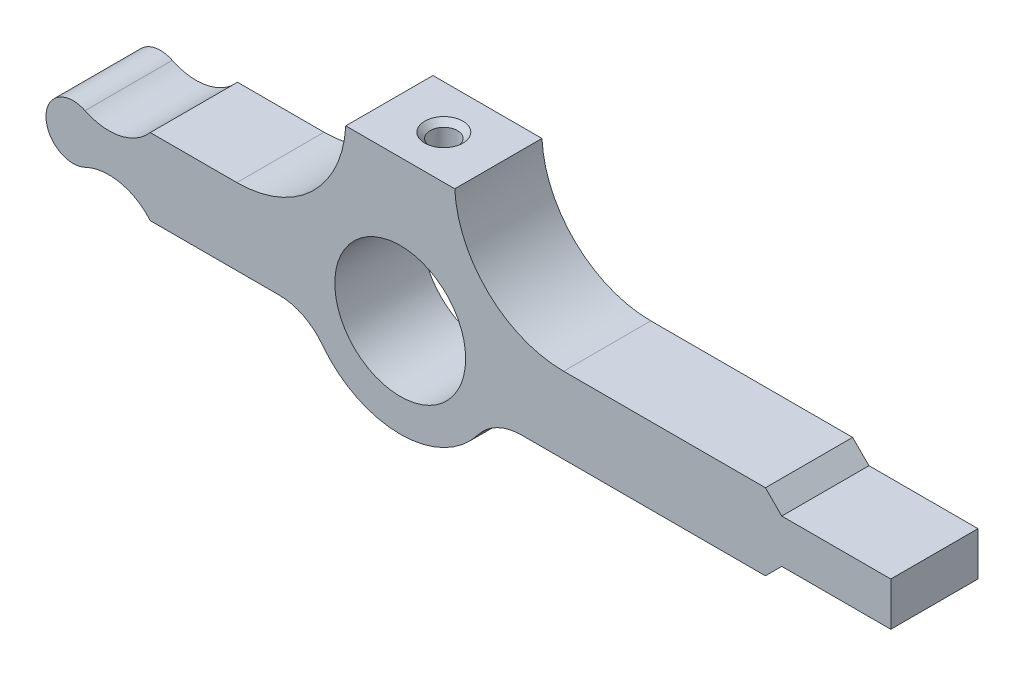
SolidWorks part; units mm, degrees
material "Латунь"
ref_plane "Спереди" through (0, 0, 0) normal (0, 0, 1) x (1, 0, 0)
ref_plane "Сверху" through (0, 0, 0) normal (0, 1, 0) x (1, 0, 0)
ref_plane "Справа" through (0, 0, 0) normal (1, 0, 0) x (0, 0, -1)
other "Таблицы"
sketch "Эскиз1" plane through (0, 0, 0) normal (0, 0, 1) x (1, 0, 0)
  line L0 (0, -12.0069) -> (0, 16.897) construction
  line L1 (-35.289, 0) -> (48.5036, 0) construction
  line L2 (11.1243, -3.5) -> (33.5, -3.5)
  line L3 (33.5, -3.5) -> (35, -2)
  line L4 (35, -2) -> (45, -2)
  line L5 (45, -2) -> (45, 2)
  line L6 (45, 2) -> (35, 2)
  line L7 (35, 2) -> (33.5, 3.5)
  line L8 (33.5, 3.5) -> (14.9875, 3.5)
  line L9 (5, 13) -> (-5, 13)
  line L10 (-14.9875, 3.5) -> (-22.9312, 3.5)
  line L11 (-22.9312, -3.5) -> (-11.1243, -3.5)
  circle A0 centre (0, 0) radius 6
  arc A1 (-7.1513, -5.4643) -> (7.1513, -5.4643) centre (0, 0) ccw
  arc A2 (5, 13) -> (14.9875, 3.5) centre (14.9875, 13.5) ccw
  arc A3 (-5, 13) -> (-14.9875, 3.5) centre (-14.9875, 13.5) cw
  arc A4 (-22.9312, 3.5) -> (-28.9103, 2.25) centre (-26.7308, 6.75) cw
  arc A5 (-28.9103, 2.25) -> (-28.9103, -2.25) centre (-30, 0) ccw
  arc A6 (-28.9103, -2.25) -> (-22.9312, -3.5) centre (-26.7308, -6.75) cw
  arc A7 (7.1513, -5.4643) -> (11.1243, -3.5) centre (11.1243, -8.5) cw
  arc A8 (-11.1243, -3.5) -> (-7.1513, -5.4643) centre (-11.1243, -8.5) cw
  dimension "D21" = 12
  dimension "D4" = 10
  dimension "D5" = 3.5
  dimension "D13" = 5
  dimension "D14" = 9
  dimension "D16" = 5
  dimension "D12" = 2.5
  dimension "D18" = 22
  dimension "D22" = 10
  dimension "D6" = 7
  dimension "D8" = 4
  dimension "D10" = 10
  dimension "D11" = 45
  dimension "L1" = 32.5
  dimension "L2" = 45
extrude "Бобышка-Вытянуть1" add sketch "Эскиз1" along normal mid plane 8
hole_wizard "Отверстие обработанное метчиком M31" positions "Эскиз5" profile "Эскиз4" tap size "M3" standard "ISO" end condition up to next
sketch "Эскиз5" plane through (0, 13, 0) normal (0, 1, 0) x (1, 0, 0)
  point P0 (0, 0)
sketch "Эскиз4" plane through (0, 13, 0) normal (1, 0, 0) x (0, 0, 1)
  line L0 (0, 0) -> (0, 7)
  line L1 (0, 7) -> (1.25, 7)
  line L2 (1.25, 7) -> (1.25, 0.5)
  line L3 (1.25, 0.5) -> (1.75, 0)
  line L5 (1.75, 0) -> (0, 0)
  line L6 (-1.25, 0.5) -> (-1.75, 0) construction
  line L11 (0, -6.35) -> (0, 107.95) construction
  dimension "Диаметр проходного сверла" = 2.5
  dimension "Глубина проходного сверла" = 7
  dimension "Диаметр передней зенковки" = 3.5
  dimension "Угол передней зенковки" = 90
cosmetic thread "Отверстие резьбы1" parameters "D2"=3
